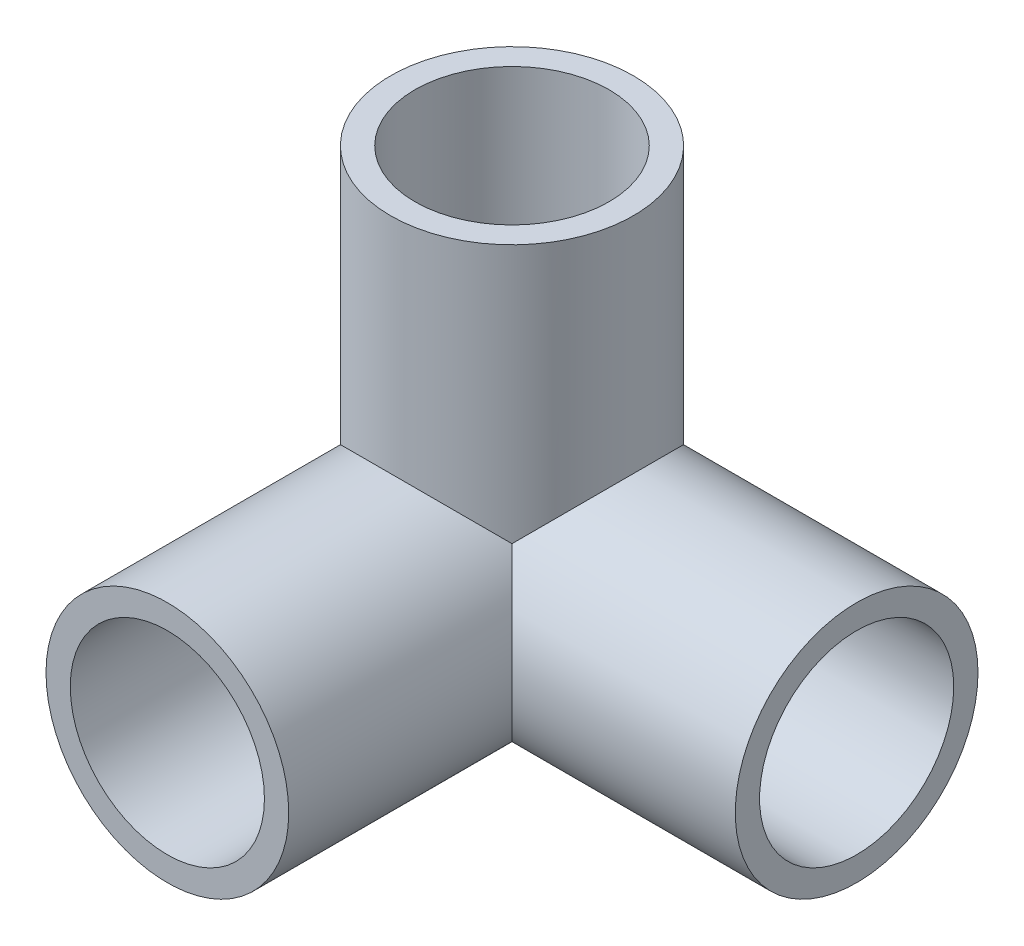
SolidWorks part; units mm, degrees
ref_plane "前视基准面" through (0, 0, 0) normal (0, 0, 1) x (1, 0, 0)
ref_plane "上视基准面" through (0, 0, 0) normal (0, 1, 0) x (1, 0, 0)
ref_plane "右视基准面" through (0, 0, 0) normal (1, 0, 0) x (0, 0, -1)
sketch "草图1" plane through (0, 0, 0) normal (0, 0, 1) x (1, 0, 0)
  line L0 (0, -1000) -> (0, 49000) construction
  circle A0 centre (0, 0) radius 10
  dimension "D1" = 20
revolve "旋转1" add sketch "草图1" angle 360 about L0 region at (4.2441, 0, 0)
sketch "草图2" plane through (0, 0, 0) normal (0, 0, 1) x (1, 0, 0)
  circle A1 centre (0, 0) radius 10
  dimension "D1" = 20
extrude "凸台-拉伸1" add sketch "草图2" along normal blind 35.5
sketch "草图3" plane through (0, 0, 0) normal (0, 1, 0) x (1, 0, 0)
  circle A1 centre (0, 0) radius 10
  dimension "D1" = 20
extrude "凸台-拉伸2" add sketch "草图3" along normal blind 35.5
sketch "草图4" plane through (0, 0, 0) normal (1, 0, 0) x (0, 0, -1)
  circle A1 centre (0, 0) radius 10
  dimension "D2" = 20
extrude "凸台-拉伸3" add sketch "草图4" along normal blind 35.5
shell "抽壳1" thickness 2.5 removed face at (10, 0, 35.5) removed face at (0, 35.5, 10) removed face at (35.5, 0, -10) outward yes
